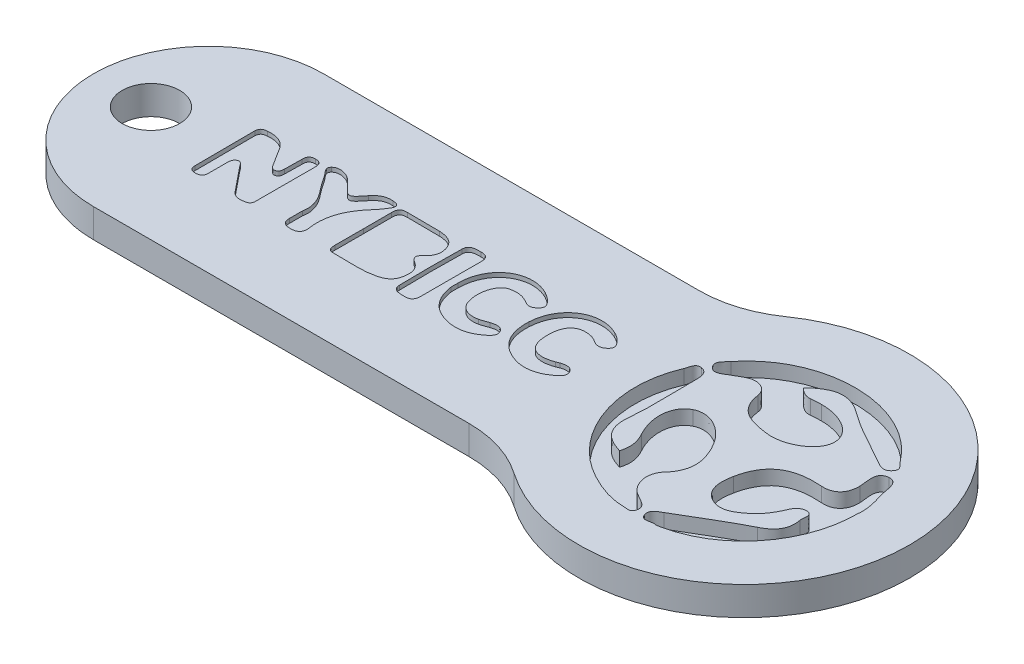
SolidWorks part; units mm, degrees
ref_plane "Plan de face" through (0, 0, 0) normal (0, 0, 1) x (1, 0, 0)
ref_plane "Plan de dessus" through (0, 0, 0) normal (0, 1, 0) x (1, 0, 0)
ref_plane "Plan de droite" through (0, 0, 0) normal (1, 0, 0) x (0, 0, -1)
sketch "Esquisse1" plane through (0, 0, 0) normal (0, 1, 0) x (1, 0, 0)
  line L0 (-14.5, 0) -> (0, 0) construction
  line L1 (-18.5, 8) -> (18.5, 8)
  line L2 (-18.5, 8) -> (-18.5, -8)
  line L3 (-18.5, -8) -> (18.5, -8)
  line L5 (-18.5, 8) -> (18.5, -8) construction
  line L6 (-18.5, -8) -> (18.5, 8) construction
  arc A0 (18.5, -8) -> (18.5, 8) centre (26.7614, 0) ccw
  circle A1 centre (-14.5, 0) radius 2
  point P0 (0, 0)
  dimension "D3" = 23
  dimension "D5" = 4
  dimension "D1" = 37
  dimension "D2" = 16
  dimension "D4" = 4
extrude "Boss.-Extru.1" add sketch "Esquisse1" along normal blind 2
sketch "Esquisse2" plane through (0, 2, 0) normal (0, 1, 0) x (1, 0, 0)
  line L0 (20.6551, -5.913) -> (-11.0872, -5.913)
  line L1 (-11.0872, -5.913) -> (-11.0872, 5.913)
  line L2 (-11.0872, 5.913) -> (20.6551, 5.913)
  line L3 (20.6551, 5.913) -> (20.5787, 5.7726)
  line L7 (18.5, 8) -> (-18.5, 8)
  line L8 (-18.5, 8) -> (-18.5, -8)
  line L9 (-18.5, -8) -> (18.5, -8)
  line L10 (18.5, 8) -> (-18.5, 8)
  line L11 (-18.5, 8) -> (-18.5, -8)
  line L12 (-18.5, -8) -> (18.5, -8)
  arc A2 (20.6551, -5.913) -> (20.6551, 5.913) centre (26.7614, 0) ccw
  arc A3 (20.6551, -5.913) -> (20.6551, 5.913) centre (26.7614, 0) ccw
  arc A4 (18.5, -8) -> (18.5, 8) centre (26.7614, 0) ccw
  arc A5 (18.5, -8) -> (18.5, 8) centre (26.7614, 0) ccw
  spline S0 degree 3 poles (0.225, -1.9246) (0.2286, -1.2609) (0.2275, -0.5975) (0.2283, 0.0661) knots 10 10 10 10 11 11 11 11
  spline S1 degree 3 poles (0.6284, -2.4527) (0.2813, -2.4644) (0.2234, -2.2089) (0.225, -1.9246) knots 9 9 9 9 10 10 10 10
  spline S2 degree 3 poles (3.5067, -2.3468) (2.5542, -2.5708) (1.5879, -2.4206) (0.6284, -2.4527) knots 8 8 8 8 9 9 9 9
  spline S3 degree 3 poles (4.4683, -1.5249) (4.3523, -2.028) (3.9703, -2.238) (3.5067, -2.3468) knots 7 7 7 7 8 8 8 8
  spline S4 degree 3 poles (4.0132, -0.175) (4.5319, -0.4973) (4.5922, -0.9877) (4.4683, -1.5249) knots 6 6 6 6 7 7 7 7
  spline S5 degree 3 poles (3.9341, 0.5259) (3.6149, 0.2483) (3.6818, 0.0309) (4.0132, -0.175) knots 5 5 5 5 6 6 6 6
  spline S6 degree 3 poles (4.2394, 1.8576) (4.4545, 1.3474) (4.3569, 0.8935) (3.9341, 0.5259) knots 4 4 4 4 5 5 5 5
  spline S7 degree 3 poles (3.0323, 2.5476) (3.5345, 2.5261) (4.0161, 2.3873) (4.2394, 1.8576) knots 3 3 3 3 4 4 4 4
  spline S8 degree 3 poles (0.7853, 2.5646) (1.5338, 2.5425) (2.2844, 2.5795) (3.0323, 2.5476) knots 2 2 2 2 3 3 3 3
  spline S9 degree 3 poles (0.2259, 1.9923) (0.215, 2.3984) (0.3606, 2.5772) (0.7853, 2.5646) knots 1 1 1 1 2 2 2 2
  spline S10 degree 3 poles (0.2283, 0.0661) (0.2291, 0.7082) (0.243, 1.3507) (0.2259, 1.9923) knots 0 0 0 0 1 1 1 1
  spline S11 degree 3 poles (-5.1722, 2.1197) (-5.1775, 1.4133) (-5.1754, 0.7068) (-5.176, 0.0003) knots 18 18 18 18 19 19 19 19
  spline S12 degree 3 poles (-5.6399, 2.5867) (-5.3196, 2.5835) (-5.1698, 2.4412) (-5.1722, 2.1197) knots 17 17 17 17 18 18 18 18
  spline S13 degree 3 poles (-6.0939, 2.115) (-6.0989, 2.4345) (-5.9709, 2.5902) (-5.6399, 2.5867) knots 16 16 16 16 17 17 17 17
  spline S14 degree 3 poles (-6.114, 0.896) (-6.0883, 1.3013) (-6.0877, 1.7087) (-6.0939, 2.115) knots 15 15 15 15 16 16 16 16
  spline S15 degree 3 poles (-6.3567, 0.4874) (-6.1454, 0.5282) (-6.1242, 0.7367) (-6.114, 0.896) knots 14 14 14 14 15 15 15 15
  spline S16 degree 3 poles (-6.7563, 0.7516) (-6.663, 0.6061) (-6.5561, 0.4488) (-6.3567, 0.4874) knots 13 13 13 13 14 14 14 14
  spline S17 degree 3 poles (-7.4724, 1.8877) (-7.2442, 1.5028) (-6.998, 1.1285) (-6.7563, 0.7516) knots 12 12 12 12 13 13 13 13
  spline S18 degree 3 poles (-8.9993, 2.5914) (-8.3468, 2.6534) (-7.8223, 2.4779) (-7.4724, 1.8877) knots 11 11 11 11 12 12 12 12
  spline S19 degree 3 poles (-9.4508, 2.1725) (-9.4369, 2.4583) (-9.2899, 2.5782) (-8.9993, 2.5914) knots 10 10 10 10 11 11 11 11
  spline S20 degree 3 poles (-9.4291, -2.0014) (-9.4372, -0.6101) (-9.4441, 0.7812) (-9.4508, 2.1725) knots 9 9 9 9 10 10 10 10
  spline S21 degree 3 poles (-9.0021, -2.437) (-9.2963, -2.4301) (-9.4357, -2.2901) (-9.4291, -2.0014) knots 8 8 8 8 9 9 9 9
  spline S22 degree 3 poles (-8.5069, -2.0014) (-8.512, -2.3343) (-8.6938, -2.4441) (-9.0021, -2.437) knots 7 7 7 7 8 8 8 8
  spline S23 degree 3 poles (-8.5036, -0.717) (-8.5043, -1.1452) (-8.5101, -1.5733) (-8.5069, -2.0014) knots 6 6 6 6 7 7 7 7
  spline S24 degree 3 poles (-8.2858, -0.219) (-8.4821, -0.3042) (-8.5032, -0.5178) (-8.5036, -0.717) knots 5 5 5 5 6 6 6 6
  spline S25 degree 3 poles (-7.8369, -0.4857) (-7.953, -0.3438) (-8.0529, -0.1181) (-8.2858, -0.219) knots 4 4 4 4 5 5 5 5
  spline S26 degree 3 poles (-6.4635, -2.1807) (-6.9172, -1.6123) (-7.376, -1.0481) (-7.8369, -0.4857) knots 3 3 3 3 4 4 4 4
  spline S27 degree 3 poles (-5.4688, -2.4272) (-5.8242, -2.5108) (-6.1923, -2.5206) (-6.4635, -2.1807) knots 2 2 2 2 3 3 3 3
  spline S28 degree 3 poles (-5.1794, -1.7337) (-5.182, -2.003) (-5.1008, -2.3406) (-5.4688, -2.4272) knots 1 1 1 1 2 2 2 2
  spline S29 degree 3 poles (-5.176, 0.0003) (-5.1766, -0.5777) (-5.174, -1.1557) (-5.1794, -1.7337) knots 0 0 0 0 1 1 1 1
  spline S30 degree 3 poles (14.6022, 1.5071) (13.5928, 1.7408) (13.0414, 1.2329) (13.0294, 0.0773) knots 11 11 11 11 12 12 12 12
  spline S31 degree 3 poles (15.1149, 1.2613) (14.9529, 1.3592) (14.7827, 1.4653) (14.6022, 1.5071) knots 10 10 10 10 11 11 11 11
  spline S32 degree 3 poles (15.9779, 1.4079) (15.76, 1.1539) (15.4505, 1.0583) (15.1149, 1.2613) knots 9 9 9 9 10 10 10 10
  spline S33 degree 3 poles (15.7902, 2.127) (15.9828, 1.9215) (16.214, 1.683) (15.9779, 1.4079) knots 8 8 8 8 9 9 9 9
  spline S34 degree 3 poles (15.1624, 2.5592) (15.3993, 2.452) (15.6134, 2.3158) (15.7902, 2.127) knots 7 7 7 7 8 8 8 8
  spline S35 degree 3 poles (11.588, 0.203) (11.6856, 2.2051) (13.4456, 3.3361) (15.1624, 2.5592) knots 6 6 6 6 7 7 7 7
  spline S36 degree 3 poles (12.9311, -2.3704) (11.8989, -1.8387) (11.5353, -0.8789) (11.588, 0.203) knots 5 5 5 5 6 6 6 6
  spline S37 degree 3 poles (15.6465, -2.1778) (14.7863, -2.8026) (13.8563, -2.8469) (12.9311, -2.3704) knots 4 4 4 4 5 5 5 5
  spline S38 degree 3 poles (16.0103, -1.3913) (16.2116, -1.7555) (15.9033, -1.9912) (15.6465, -2.1778) knots 3 3 3 3 4 4 4 4
  spline S39 degree 3 poles (15.1543, -1.1929) (15.4802, -1.0869) (15.8296, -1.0644) (16.0103, -1.3913) knots 2 2 2 2 3 3 3 3
  spline S40 degree 3 poles (14.9188, -1.2919) (14.9993, -1.2645) (15.0736, -1.2191) (15.1543, -1.1929) knots 1 1 1 1 2 2 2 2
  spline S41 degree 3 poles (13.0294, 0.0773) (13.0157, -1.2291) (13.6832, -1.7132) (14.9188, -1.2919) knots 0 0 0 0 1 1 1 1
  spline S42 degree 3 poles (6.7883, -0.4372) (6.7642, -0.2695) (6.7853, -0.0953) (6.7855, 0.0759) knots 13 13 13 13 14 14 14 14
  spline S43 degree 3 poles (8.2655, -2.4564) (7.3765, -2.0939) (6.9224, -1.3698) (6.7883, -0.4372) knots 12 12 12 12 13 13 13 13
  spline S44 degree 3 poles (10.8143, -2.1643) (10.0263, -2.763) (9.1527, -2.8182) (8.2655, -2.4564) knots 11 11 11 11 12 12 12 12
  spline S45 degree 3 poles (11.1531, -1.3675) (11.3657, -1.7257) (11.0713, -1.969) (10.8143, -2.1643) knots 10 10 10 10 11 11 11 11
  spline S46 degree 3 poles (10.2831, -1.1939) (10.6037, -1.0968) (10.9594, -1.0413) (11.1531, -1.3675) knots 9 9 9 9 10 10 10 10
  spline S47 degree 3 poles (9.6778, -1.3958) (9.8846, -1.3539) (10.0795, -1.2556) (10.2831, -1.1939) knots 8 8 8 8 9 9 9 9
  spline S48 degree 3 poles (8.2731, -0.709) (8.4644, -1.2666) (8.9952, -1.5338) (9.6778, -1.3958) knots 7 7 7 7 8 8 8 8
  spline S49 degree 3 poles (8.7857, 1.4455) (8.2295, 1.1729) (7.9857, 0.1288) (8.2731, -0.709) knots 6 6 6 6 7 7 7 7
  spline S50 degree 3 poles (9.155, 1.5328) (9.0302, 1.5112) (8.8966, 1.4998) (8.7857, 1.4455) knots 5 5 5 5 6 6 6 6
  spline S51 degree 3 poles (10.3714, 1.2365) (9.9944, 1.4594) (9.6027, 1.6104) (9.155, 1.5328) knots 4 4 4 4 5 5 5 5
  spline S52 degree 3 poles (11.1159, 1.4051) (10.9208, 1.1953) (10.6661, 1.0622) (10.3714, 1.2365) knots 3 3 3 3 4 4 4 4
  spline S53 degree 3 poles (10.9947, 2.0797) (11.1716, 1.8988) (11.3491, 1.6561) (11.1159, 1.4051) knots 2 2 2 2 3 3 3 3
  spline S54 degree 3 poles (10.3813, 2.5334) (10.6062, 2.4205) (10.8187, 2.2596) (10.9947, 2.0797) knots 1 1 1 1 2 2 2 2
  spline S55 degree 3 poles (6.7855, 0.0759) (6.7712, 2.1623) (8.6141, 3.4209) (10.3813, 2.5334) knots 0 0 0 0 1 1 1 1
  spline S56 degree 3 poles (20.8247, -2.0529) (20.69, -3.4272) (21.2917, -4.0532) (22.4958, -4.411) knots 13 13 13 13 14 14 14 14
  spline S57 degree 3 poles (20.8707, 2.5877) (20.8518, 1.04) (20.975, -0.5195) (20.8247, -2.0529) knots 12 12 12 12 13 13 13 13
  spline S58 degree 3 poles (20.3589, 3.4373) (20.7757, 3.356) (20.8759, 3.0031) (20.8707, 2.5877) knots 11 11 11 11 12 12 12 12
  spline S59 degree 3 poles (19.7877, 2.7925) (19.904, 3.0638) (19.9018, 3.5264) (20.3589, 3.4373) knots 10 10 10 10 11 11 11 11
  spline S60 degree 3 poles (23.1867, -6.7698) (19.8096, -4.9332) (18.3001, -0.6793) (19.7877, 2.7925) knots 9 9 9 9 10 10 10 10
  spline S61 degree 3 poles (25.9567, -7.6289) (24.9549, -7.6033) (24.0484, -7.2383) (23.1867, -6.7698) knots 8 8 8 8 9 9 9 9
  spline S62 degree 3 poles (26.6612, -7.3752) (26.5599, -7.7864) (26.214, -7.6353) (25.9567, -7.6289) knots 7 7 7 7 8 8 8 8
  spline S63 degree 3 poles (26.268, -6.6952) (26.5299, -6.8467) (26.7435, -7.0408) (26.6612, -7.3752) knots 6 6 6 6 7 7 7 7
  spline S64 degree 3 poles (25.7401, -6.3888) (25.9117, -6.4978) (26.0918, -6.5935) (26.268, -6.6952) knots 5 5 5 5 6 6 6 6
  spline S65 degree 3 poles (25.3508, -4.1307) (24.7364, -4.8112) (24.986, -5.9092) (25.7401, -6.3888) knots 4 4 4 4 5 5 5 5
  spline S66 degree 3 poles (25.5618, -1.0872) (26.0741, -2.135) (26.252, -3.1326) (25.3508, -4.1307) knots 3 3 3 3 4 4 4 4
  spline S67 degree 3 poles (22.5765, 0.6204) (23.5077, 1.0885) (24.8768, 0.3142) (25.5618, -1.0872) knots 2 2 2 2 3 3 3 3
  spline S68 degree 3 poles (22.2705, -2.6617) (21.4852, -1.2334) (21.6533, 0.1562) (22.5765, 0.6204) knots 1 1 1 1 2 2 2 2
  spline S69 degree 3 poles (22.4958, -4.411) (22.6895, -3.7654) (22.5874, -3.2375) (22.2705, -2.6617) knots 0 0 0 0 1 1 1 1
  spline S70 degree 3 poles (34.2908, 1.9196) (34.5116, 1.2692) (34.6572, 0.5833) (34.5723, 0.043) knots 15 15 15 15 16 16 16 16
  spline S71 degree 3 poles (33.4768, 3.345) (34.1825, 3.4033) (34.1107, 2.4507) (34.2908, 1.9196) knots 14 14 14 14 15 15 15 15
  spline S72 degree 3 poles (32.9899, 1.8117) (32.9782, 2.3605) (32.6504, 3.2769) (33.4768, 3.345) knots 13 13 13 13 14 14 14 14
  spline S73 degree 3 poles (31.6503, 0.4778) (32.418, 0.4191) (33.0107, 0.8361) (32.9899, 1.8117) knots 12 12 12 12 13 13 13 13
  spline S74 degree 3 poles (28.0087, -2.0014) (28.3864, -0.1074) (29.5871, 0.6354) (31.6503, 0.4778) knots 11 11 11 11 12 12 12 12
  spline S75 degree 3 poles (28.7232, -4.1459) (27.8705, -3.6814) (27.8418, -2.8385) (28.0087, -2.0014) knots 10 10 10 10 11 11 11 11
  spline S76 degree 3 poles (30.8285, -3.6402) (30.2151, -4.1482) (29.5238, -4.582) (28.7232, -4.1459) knots 9 9 9 9 10 10 10 10
  spline S77 degree 3 poles (31.9149, -2.0477) (31.6643, -2.6604) (31.3386, -3.2179) (30.8285, -3.6402) knots 8 8 8 8 9 9 9 9
  spline S78 degree 3 poles (32.6672, -1.5283) (32.3502, -1.494) (32.0434, -1.7332) (31.9149, -2.0477) knots 7 7 7 7 8 8 8 8
  spline S79 degree 3 poles (32.9603, -2.3153) (32.9084, -2.0339) (33.1548, -1.5813) (32.6672, -1.5283) knots 6 6 6 6 7 7 7 7
  spline S80 degree 3 poles (31.9014, -4.2266) (32.7588, -3.7947) (33.1312, -3.2385) (32.9603, -2.3153) knots 5 5 5 5 6 6 6 6
  spline S81 degree 3 poles (27.7784, -6.5813) (29.1518, -5.7938) (30.49, -4.9378) (31.9014, -4.2266) knots 4 4 4 4 5 5 5 5
  spline S82 degree 3 poles (27.221, -7.3854) (27.066, -6.9234) (27.4568, -6.7657) (27.7784, -6.5813) knots 3 3 3 3 4 4 4 4
  spline S83 degree 3 poles (28.1667, -7.6063) (27.8477, -7.5375) (27.3951, -7.903) (27.221, -7.3854) knots 2 2 2 2 3 3 3 3
  spline S84 degree 3 poles (28.5281, -7.569) (28.4093, -7.5932) (28.2794, -7.6307) (28.1667, -7.6063) knots 1 1 1 1 2 2 2 2
  spline S85 degree 3 poles (34.5723, 0.043) (34.5572, -3.6847) (31.9805, -6.8615) (28.5281, -7.569) knots 0 0 0 0 1 1 1 1
  spline S86 degree 3 poles (-2.9715, -1.8867) (-2.973, -1.6296) (-2.9712, -1.3724) (-2.9707, -0.9865) knots 12 12 12 12 13 13 13 13
  spline S87 degree 3 poles (-2.3827, -2.4792) (-2.7888, -2.4647) (-2.9692, -2.2761) (-2.9715, -1.8867) knots 11 11 11 11 12 12 12 12
  spline S88 degree 3 poles (-1.7083, -1.7964) (-1.6343, -2.2893) (-1.886, -2.4971) (-2.3827, -2.4792) knots 10 10 10 10 11 11 11 11
  spline S89 degree 3 poles (-0.5499, 1.5886) (-1.4324, 0.6279) (-1.9089, -0.4619) (-1.7083, -1.7964) knots 9 9 9 9 10 10 10 10
  spline S90 degree 3 poles (-0.1364, 2.159) (-0.265, 1.9625) (-0.392, 1.7605) (-0.5499, 1.5886) knots 8 8 8 8 9 9 9 9
  spline S91 degree 3 poles (-0.4448, 2.7623) (0.0585, 2.7305) (0.1083, 2.5327) (-0.1364, 2.159) knots 7 7 7 7 8 8 8 8
  spline S92 degree 3 poles (-1.5894, 2.2197) (-1.281, 2.6095) (-0.9475, 2.7942) (-0.4448, 2.7623) knots 6 6 6 6 7 7 7 7
  spline S93 degree 3 poles (-2.9946, 2.1544) (-2.2746, 1.3894) (-2.2599, 1.3721) (-1.5894, 2.2197) knots 5 5 5 5 6 6 6 6
  spline S94 degree 3 poles (-3.569, 2.6592) (-3.3482, 2.549) (-3.1695, 2.3403) (-2.9946, 2.1544) knots 4 4 4 4 5 5 5 5
  spline S95 degree 3 poles (-4.5969, 2.6437) (-4.3452, 2.899) (-3.899, 2.8238) (-3.569, 2.6592) knots 3 3 3 3 4 4 4 4
  spline S96 degree 3 poles (-4.318, 1.8864) (-4.4694, 2.1215) (-4.86, 2.3768) (-4.5969, 2.6437) knots 2 2 2 2 3 3 3 3
  spline S97 degree 3 poles (-3.6134, 0.892) (-3.8691, 1.2068) (-4.0981, 1.5451) (-4.318, 1.8864) knots 1 1 1 1 2 2 2 2
  spline S98 degree 3 poles (-2.9707, -0.9865) (-2.8232, -0.3301) (-3.1349, 0.3025) (-3.6134, 0.892) knots 0 0 0 0 1 1 1 1
  spline S99 degree 3 poles (28.4489, 6.1036) (27.188, 7.04) (26.1934, 6.8331) (25.1006, 5.7726) knots 13 13 13 13 14 14 14 14
  spline S100 degree 3 poles (32.2257, 3.8741) (30.9697, 4.6247) (29.6158, 5.2371) (28.4489, 6.1036) knots 12 12 12 12 13 13 13 13
  spline S101 degree 3 poles (33.1947, 3.8749) (32.8996, 3.5244) (32.5762, 3.6646) (32.2257, 3.8741) knots 11 11 11 11 12 12 12 12
  spline S102 degree 3 poles (32.9181, 4.6879) (33.0852, 4.4632) (33.51, 4.2491) (33.1947, 3.8749) knots 10 10 10 10 11 11 11 11
  spline S103 degree 3 poles (21.0052, 4.8289) (23.9283, 8.5635) (30.0923, 8.4884) (32.9181, 4.6879) knots 9 9 9 9 10 10 10 10
  spline S104 degree 3 poles (20.6512, 3.9116) (20.3706, 4.3111) (20.8091, 4.5784) (21.0052, 4.8289) knots 8 8 8 8 9 9 9 9
  spline S105 degree 3 poles (21.7112, 3.951) (21.3602, 3.7373) (20.9758, 3.4496) (20.6512, 3.9116) knots 7 7 7 7 8 8 8 8
  spline S106 degree 3 poles (22.4531, 4.3729) (22.1989, 4.2458) (21.9541, 4.099) (21.7112, 3.951) knots 6 6 6 6 7 7 7 7
  spline S107 degree 3 poles (23.9755, 3.7431) (23.8907, 4.348) (23.204, 4.7486) (22.4531, 4.3729) knots 5 5 5 5 6 6 6 6
  spline S108 degree 3 poles (26.5035, 1.7576) (25.3358, 1.9291) (24.1957, 2.1695) (23.9755, 3.7431) knots 4 4 4 4 5 5 5 5
  spline S109 degree 3 poles (29.457, 3.5205) (29.4094, 2.5046) (27.9199, 1.5498) (26.5035, 1.7576) knots 3 3 3 3 4 4 4 4
  spline S110 degree 3 poles (26.7445, 5.4024) (28.3033, 5.391) (29.5054, 4.5538) (29.457, 3.5205) knots 2 2 2 2 3 3 3 3
  spline S111 degree 3 poles (26.0136, 5.3603) (26.2569, 5.3802) (26.5009, 5.4042) (26.7445, 5.4024) knots 1 1 1 1 2 2 2 2
  spline S112 degree 3 poles (25.1006, 5.7726) (25.3972, 5.4799) (25.6664, 5.3319) (26.0136, 5.3603) knots 0 0 0 0 1 1 1 1
  spline S113 degree 3 poles (6.2957, 2.1656) (6.2889, 1.4614) (6.2923, 0.7571) (6.2917, 0.0529) knots 6 6 6 6 7 7 7 7
  spline S114 degree 3 poles (5.7113, 2.7436) (6.1126, 2.754) (6.2995, 2.5672) (6.2957, 2.1656) knots 5 5 5 5 6 6 6 6
  spline S115 degree 3 poles (4.8778, 2.2684) (4.8908, 2.7581) (5.3424, 2.734) (5.7113, 2.7436) knots 4 4 4 4 5 5 5 5
  spline S116 degree 3 poles (4.8746, -2.0826) (4.8408, -0.6328) (4.8396, 0.8188) (4.8778, 2.2684) knots 3 3 3 3 4 4 4 4
  spline S117 degree 3 poles (5.7365, -2.5991) (5.3325, -2.5938) (4.8868, -2.606) (4.8746, -2.0826) knots 2 2 2 2 3 3 3 3
  spline S118 degree 3 poles (6.2899, -1.9959) (6.2905, -2.369) (6.1719, -2.6048) (5.7365, -2.5991) knots 1 1 1 1 2 2 2 2
  spline S119 degree 3 poles (6.2917, 0.0529) (6.2911, -0.63) (6.2888, -1.313) (6.2899, -1.9959) knots 0 0 0 0 1 1 1 1
  dimension "D1" = 3
  dimension "D2" = 0
sketch "Esquisse3" plane through (0, 2, 0) normal (0, 1, 0) x (1, 0, 0)
  line L0 (-18.5, -8) -> (18.5, -8) construction
  line L1 (18.5, 8) -> (-18.5, 8) construction
  line L2 (-18.5, 8) -> (-18.5, -8) construction
  line L3 (-18.5, -8) -> (18.5, -8)
  line L4 (18.5, 8) -> (-18.5, 8)
  line L5 (-18.5, 8) -> (-18.5, -8)
  line L6 (20.6551, -5.913) -> (-11.0872, -5.913) construction
  line L7 (-11.0872, -5.913) -> (-11.0872, 5.913) construction
  line L8 (-11.0872, 5.913) -> (20.6551, 5.913) construction
  line L9 (20.6551, -5.913) -> (-11.0872, -5.913)
  line L10 (-11.0872, -5.913) -> (-11.0872, 5.913)
  line L11 (-11.0872, 5.913) -> (20.6551, 5.913)
  arc A0 (18.5, -8) -> (18.5, 8) centre (26.7614, 0) ccw construction
  arc A1 (18.5, -8) -> (18.5, 8) centre (26.7614, 0) ccw
  arc A2 (20.6551, -5.913) -> (20.6551, 5.913) centre (26.7614, 0) ccw construction
  arc A3 (20.6551, -5.913) -> (20.6551, 5.913) centre (26.7614, 0) ccw
  circle A4 centre (-14.5, 0) radius 2 construction
  circle A5 centre (-14.5, 0) radius 2
sketch "Esquisse4" plane through (0, 2, 0) normal (0, 1, 0) x (1, 0, 0)
  line L0 (20.6551, 5.913) -> (20.5787, 5.7726) construction
  line L7 (20.6551, 5.913) -> (20.5787, 5.7726)
  spline S0 degree 3 poles (-1984.6159, -235.4176) (1984.8667, 57.9946) (-1984.2687, -59.6643) (1984.6454, 236.3676) knots -55.998309 -55.998309 -55.998309 -55.998309 77.422102 77.422102 77.422102 77.422102 only from (0.225, -1.9246) to (0.2283, 0.0661) construction
  spline S1 degree 3 poles (1999.7349, -15.7658) (-1999.9355, -74.5215) (2000.3921, 75.7285) (-1999.2541, 17.2511) knots -35.375256 -35.375256 -35.375256 -35.375256 35.969237 35.969237 35.969237 35.969237 only from (0.2283, 0.0661) to (0.2259, 1.9923) construction
  spline S2 degree 3 poles (-1692.3905, -1052.1639) (1808.7885, 680.6818) (-1908.2396, -373.9881) (1993.8725, 140.0338) knots -24.33099 -24.33099 -24.33099 -24.33099 25.117482 25.117482 25.117482 25.117482 only from (0.2259, 1.9923) to (0.7853, 2.5646) construction
  spline S3 degree 3 poles (21.6545, 2002.1445) (-93.1428, -1997.5504) (96.9755, 2002.6751) (-18.569, -1997.045) knots -22.540346 -22.540346 -22.540346 -22.540346 27.463763 27.463763 27.463763 27.463763 only from (0.7853, 2.5646) to (3.0323, 2.5476) construction
  spline S4 degree 3 poles (1342.8316, 1487.3667) (-1343.1752, -1508.655) (1318.8645, 1538.4795) (-1249.0693, -1556.4903) knots -15.00696 -15.00696 -15.00696 -15.00696 20.437547 20.437547 20.437547 20.437547 only from (3.0323, 2.5476) to (4.2394, 1.8576) construction
  spline S5 degree 3 poles (-758.8387, -1790.0698) (-384.1825, 1710.4209) (1110.0246, -1522.0891) (-1512.5494, 1293.8524) knots -37.495623 -37.495623 -37.495623 -37.495623 37.718737 37.718737 37.718737 37.718737 only from (4.2394, 1.8576) to (3.9341, 0.5259) construction
  spline S6 degree 3 poles (1901.3277, 632.4127) (-1933.3024, -702.9617) (1907.3667, 801.0653) (-1760.1231, -939.1778) knots -17.085348 -17.085348 -17.085348 -17.085348 32.880542 32.880542 32.880542 32.880542 only from (3.9341, 0.5259) to (4.0132, -0.175) construction
  spline S7 degree 3 poles (-1846.1792, -759.1673) (1864.6087, 816.5198) (-1848.0317, -842.6889) (1829.127, 817.172) knots -11.270564 -11.270564 -11.270564 -11.270564 26.527108 26.527108 26.527108 26.527108 only from (4.0132, -0.175) to (4.4683, -1.5249) construction
  spline S8 degree 3 poles (-1354.7293, 1465.4733) (1405.9497, -1460.4078) (-1406.7612, 1449.9158) (1379.4873, -1453.6486) knots -11.155139 -11.155139 -11.155139 -11.155139 28.131848 28.131848 28.131848 28.131848 only from (4.4683, -1.5249) to (3.5067, -2.3468) construction
  spline S9 degree 3 poles (-28.5631, 1997.2346) (90.6759, -2003.8054) (-87.5575, 1998.8408) (31.7925, -2002.0232) knots -6.648346 -6.648346 -6.648346 -6.648346 23.992993 23.992993 23.992993 23.992993 only from (3.5067, -2.3468) to (0.6284, -2.4527) construction
  spline S10 degree 3 poles (1411.4689, 1415.0021) (-1401.3499, -1450.1488) (1390.9958, 1457.3173) (-1378.561, -1450.6074) knots -8.05933 -8.05933 -8.05933 -8.05933 28.435848 28.435848 28.435848 28.435848 only from (0.6284, -2.4527) to (0.225, -1.9246) construction
  spline S11 degree 3 poles (-97.8956, -1981.1768) (690.426, 1506.3572) (-1281.6463, -874.2833) (1979.2178, 67.1058) knots -10.529402 -10.529402 -10.529402 -10.529402 35.566895 35.566895 35.566895 35.566895 only from (14.6022, 1.5071) to (13.0294, 0.0773) construction
  spline S12 degree 3 poles (1949.7679, 398.3881) (-1397.5696, 433.0176) (848.2959, -1224.1896) (-194.4399, 1965.5178) knots -20.941126 -20.941126 -20.941126 -20.941126 21.868417 21.868417 21.868417 21.868417 only from (13.0294, 0.0773) to (14.9188, -1.2919) construction
  spline S13 degree 3 poles (-635.9133, 1889.7913) (654.3027, -1897.7039) (-624.0515, 1895.283) (665.4221, -1892.4779) knots -35.600819 -35.600819 -35.600819 -35.600819 38.569409 38.569409 38.569409 38.569409 only from (14.9188, -1.2919) to (15.1543, -1.1929) construction
  spline S14 degree 3 poles (1232.8348, 1585.2896) (-1188.5596, -1623.3311) (1181.3523, 1647.1031) (-1091.2599, -1666.6185) knots -16.478794 -16.478794 -16.478794 -16.478794 20.145313 20.145313 20.145313 20.145313 only from (15.1543, -1.1929) to (16.0103, -1.3913) construction
  spline S15 degree 3 poles (-1956.7943, 326.691) (2007.9741, -293.3837) (-1980.3817, 263.4136) (1999.6702, -253.8499) knots -11.326247 -11.326247 -11.326247 -11.326247 19.171764 19.171764 19.171764 19.171764 only from (16.0103, -1.3913) to (15.6465, -2.1778) construction
  spline S16 degree 3 poles (-972.4429, 1730.2132) (1342.4303, -1518.7994) (-1656.7274, 1035.2434) (1969.7851, -170.5391) knots -19.231438 -19.231438 -19.231438 -19.231438 35.06852 35.06852 35.06852 35.06852 only from (15.6465, -2.1778) to (12.9311, -2.3704) construction
  spline S17 degree 3 poles (1450.3278, 1386.8956) (-1356.7136, -1547.8282) (1271.6623, 1649.3112) (-1094.442, -1665.2911) knots -10.368146 -10.368146 -10.368146 -10.368146 24.205438 24.205438 24.205438 24.205438 only from (12.9311, -2.3704) to (11.588, 0.203) construction
  spline S18 degree 3 poles (1916.8799, 594.4821) (-1777.8783, -899.8956) (1637.4032, 1178.5364) (-1393.7476, -1411.3134) knots -3.492496 -3.492496 -3.492496 -3.492496 16.464951 16.464951 16.464951 16.464951 only from (11.588, 0.203) to (15.1624, 2.5592) construction
  spline S19 degree 3 poles (1002.5446, 1741.5536) (-1033.0456, -1715.8116) (1074.7683, 1713.6368) (-1014.5815, -1711.94) knots -35.983375 -35.983375 -35.983375 -35.983375 47.351842 47.351842 47.351842 47.351842 only from (15.1624, 2.5592) to (15.7902, 2.127) construction
  spline S20 degree 3 poles (2015.7301, 1.4994) (-1996.1954, -0.7141) (2027.6138, 21.579) (-1983.3114, -47.4545) knots -7.760073 -7.760073 -7.760073 -7.760073 23.910839 23.910839 23.910839 23.910839 only from (15.7902, 2.127) to (15.9779, 1.4079) construction
  spline S21 degree 3 poles (-1056.2118, -1685.326) (944.4563, 1797.9971) (-761.5857, -1864.2446) (637.7935, 1900.8501) knots -15.195035 -15.195035 -15.195035 -15.195035 31.84164 31.84164 31.84164 31.84164 only from (15.9779, 1.4079) to (15.1149, 1.2613) construction
  spline S22 degree 3 poles (69.3485, 2000.4781) (-34.7887, -2009.1821) (80.2974, 2011.1017) (-85.3785, -1995.8911) knots -20.144545 -20.144545 -20.144545 -20.144545 40.360841 40.360841 40.360841 40.360841 only from (15.1149, 1.2613) to (14.6022, 1.5071) construction
  spline S23 degree 3 poles (1991.5419, 97.7516) (-2002.0056, 32.259) (1991.6922, -33.2335) (-2002.0098, -98.7261) knots -56.370957 -56.370957 -56.370957 -56.370957 56.933317 56.933317 56.933317 56.933317 only from (-5.176, 0.0003) to (-5.1794, -1.7337) construction
  spline S24 degree 3 poles (1990.0705, 119.8329) (-2000.3981, 45.9324) (1989.9987, -44.8805) (-2000.2796, -118.3534) knots -39.486099 -39.486099 -39.486099 -39.486099 76.939646 76.939646 76.939646 76.939646 only from (-5.1722, 2.1197) to (-5.176, 0.0003) construction
  spline S25 degree 3 poles (-1514.7247, 1294.7036) (952.749, -1555.6921) (-514.9768, 1792.3506) (143.8851, -1987.0807) knots -18.57208 -18.57208 -18.57208 -18.57208 50.514202 50.514202 50.514202 50.514202 only from (-5.6399, 2.5867) to (-5.1722, 2.1197) construction
  spline S26 degree 3 poles (-1877.1306, -682.9309) (1933.1452, 262.2025) (-1979.9546, 51.1676) (1974.968, -263.0849) knots -15.916168 -15.916168 -15.916168 -15.916168 44.683452 44.683452 44.683452 44.683452 only from (-6.0939, 2.115) to (-5.6399, 2.5867) construction
  spline S27 degree 3 poles (-1984.625, 290.7016) (1972.6598, -373.7166) (-1983.3894, 389.401) (1967.9915, -317.242) knots -31.513147 -31.513147 -31.513147 -31.513147 64.250905 64.250905 64.250905 64.250905 only from (-6.114, 0.896) to (-6.0939, 2.115) construction
  spline S28 degree 3 poles (-1317.6023, 1510.4746) (1281.5296, -1540.6069) (-1271.0603, 1561.2131) (1237.2504, -1565.5542) knots -4.359551 -4.359551 -4.359551 -4.359551 34.141117 34.141117 34.141117 34.141117 only from (-6.3567, 0.4874) to (-6.114, 0.896) construction
  spline S29 degree 3 poles (-704.888, -1873.3767) (697.205, 1881.7156) (-724.356, -1874.9299) (732.3513, 1858.9379) knots -7.800082 -7.800082 -7.800082 -7.800082 33.854075 33.854075 33.854075 33.854075 only from (-6.7563, 0.7516) to (-6.3567, 0.4874) construction
  spline S30 degree 3 poles (1686.2531, 1064.9229) (-1741.5284, -998.6405) (1727.8868, 1000.3536) (-1700.5204, -1062.2751) knots -29.77822 -29.77822 -29.77822 -29.77822 55.385582 55.385582 55.385582 55.385582 only from (-7.4724, 1.8877) to (-6.7563, 0.7516) construction
  spline S31 degree 3 poles (349.9698, 1969.1657) (-518.8212, -1984.8781) (555.4811, 1972.3308) (-559.4658, -1920.3992) knots -12.744458 -12.744458 -12.744458 -12.744458 31.890927 31.890927 31.890927 31.890927 only from (-8.9993, 2.5914) to (-7.4724, 1.8877) construction
  spline S32 degree 3 poles (62.1842, -1994.5239) (156.3714, 1949.5866) (-487.3684, -1875.4729) (872.5158, 1790.3812) knots -19.56925 -19.56925 -19.56925 -19.56925 43.997523 43.997523 43.997523 43.997523 only from (-9.4508, 2.1725) to (-8.9993, 2.5914) construction
  spline S33 degree 3 poles (1868.568, -629.3467) (-1882.7149, -26.8581) (1862.2669, 29.7478) (-1882.8415, 640.3356) knots -109.086057 -109.086057 -109.086057 -109.086057 129.222482 129.222482 129.222482 129.222482 only from (-9.4291, -2.0014) to (-9.4508, 2.1725) construction
  spline S34 degree 3 poles (1858.5574, -646.0582) (-1085.6529, 1146.0776) (412.2247, -1596.9713) (105.5736, 1984.269) knots -37.811873 -37.811873 -37.811873 -37.811873 51.183123 51.183123 51.183123 51.183123 only from (-9.0021, -2.437) to (-9.4291, -2.0014) construction
  spline S35 degree 3 poles (-948.3287, 1763.2789) (906.1852, -1816.4719) (-849.586, 1848.2067) (691.9189, -1874.7093) knots -16.474382 -16.474382 -16.474382 -16.474382 35.183216 35.183216 35.183216 35.183216 only from (-8.5069, -2.0014) to (-9.0021, -2.437) construction
  spline S36 degree 3 poles (-2006.5388, 78.5807) (1990.0829, 8.6823) (-2007.117, -11.342) (1989.5957, -80.0299) knots -45.796593 -45.796593 -45.796593 -45.796593 58.515214 58.515214 58.515214 58.515214 only from (-8.5036, -0.717) to (-8.5069, -2.0014) construction
  spline S37 degree 3 poles (1488.0078, -1327.1249) (-1490.1443, 1358.907) (1458.2111, -1376.7866) (-1460.2368, 1374.8972) knots -15.192002 -15.192002 -15.192002 -15.192002 27.246672 27.246672 27.246672 27.246672 only from (-8.2858, -0.219) to (-8.5036, -0.717) construction
  spline S38 degree 3 poles (673.088, 1880.0131) (-688.1382, -1888.8072) (679.2484, 1885.4471) (-709.6456, -1873.1101) knots -12.426132 -12.426132 -12.426132 -12.426132 20.812048 20.812048 20.812048 20.812048 only from (-7.8369, -0.4857) to (-8.2858, -0.219) construction
  spline S39 degree 3 poles (-1484.655, -1345.5597) (1616.695, 1165.2864) (-1635.7671, -1162.0527) (1471.2106, 1341.657) knots -75.46992 -75.46992 -75.46992 -75.46992 84.90711 84.90711 84.90711 84.90711 only from (-6.4635, -2.1807) to (-7.8369, -0.4857) construction
  spline S40 degree 3 poles (-767.3684, -1851.5657) (756.8255, 1864.5842) (-741.1465, -1879.287) (678.4119, 1876.754) knots -17.146101 -17.146101 -17.146101 -17.146101 20.711154 20.711154 20.711154 20.711154 only from (-5.4688, -2.4272) to (-6.4635, -2.1807) construction
  spline S41 degree 3 poles (1710.8865, -1028.8932) (-1725.3117, 1036.0537) (1718.4132, -1033.9693) (-1731.5988, 1007.6235) knots -13.610126 -13.610126 -13.610126 -13.610126 15.95404 15.95404 15.95404 15.95404 only from (-5.1794, -1.7337) to (-5.4688, -2.4272) construction
  spline S42 degree 3 poles (-1967.5315, 288.8439) (2008.4862, -256.0698) (-1990.003, 227.1596) (1998.9442, -219.1607) knots -4.474592 -4.474592 -4.474592 -4.474592 26.362409 26.362409 26.362409 26.362409 only from (11.1531, -1.3675) to (10.8143, -2.1643) construction
  spline S43 degree 3 poles (1042.5899, 1711.7208) (-1017.4605, -1736.0585) (1011.4406, 1748.6428) (-942.6349, -1759.1398) knots -8.283647 -8.283647 -8.283647 -8.283647 26.187035 26.187035 26.187035 26.187035 only from (10.2831, -1.1939) to (11.1531, -1.3675) construction
  spline S44 degree 3 poles (-437.8676, 1947.8489) (436.7439, -1958.6073) (-417.5143, 1955.8514) (460.5386, -1949.8076) knots -18.995703 -18.995703 -18.995703 -18.995703 36.206708 36.206708 36.206708 36.206708 only from (9.6778, -1.3958) to (10.2831, -1.1939) construction
  spline S45 degree 3 poles (1927.2811, -546.9605) (-1762.1024, 866.6105) (1588.2179, -1178.8653) (-1333.8705, 1472.6681) knots -13.083599 -13.083599 -13.083599 -13.083599 28.316064 28.316064 28.316064 28.316064 only from (8.2731, -0.709) to (9.6778, -1.3958) construction
  spline S46 degree 3 poles (-210.3772, -1985.6489) (375.3341, 1996.5797) (-506.2668, -1963.0737) (668.3993, 1886.0938) knots -5.944932 -5.944932 -5.944932 -5.944932 19.309732 19.309732 19.309732 19.309732 only from (8.7857, 1.4455) to (8.2731, -0.709) construction
  spline S47 degree 3 poles (-1006.2355, 1724.5825) (1036.4975, -1721.3846) (-1014.2482, 1726.7744) (1012.0788, -1728.5937) knots -26.66818 -26.66818 -26.66818 -26.66818 37.096617 37.096617 37.096617 37.096617 only from (9.155, 1.5328) to (8.7857, 1.4455) construction
  spline S48 degree 3 poles (558.36, 1924.5437) (-497.6224, -1947.5948) (514.8773, 1950.5552) (-523.0983, -1926.1926) knots -19.60293 -19.60293 -19.60293 -19.60293 26.69759 26.69759 26.69759 26.69759 only from (10.3714, 1.2365) to (9.155, 1.5328) construction
  spline S49 degree 3 poles (-234.0396, -1983.3805) (213.7878, 2010.2476) (-135.5771, -2011.2908) (89.6481, 1999.4407) knots -17.879025 -17.879025 -17.879025 -17.879025 23.256703 23.256703 23.256703 23.256703 only from (11.1159, 1.4051) to (10.3714, 1.2365) construction
  spline S50 degree 3 poles (1988.0089, -299.9971) (-1982.2636, 281.7575) (2008.5743, -242.8377) (-1978.8999, 199.7886) knots -14.898875 -14.898875 -14.898875 -14.898875 18.938346 18.938346 18.938346 18.938346 only from (10.9947, 2.0797) to (11.1159, 1.4051) construction
  spline S51 degree 3 poles (1149.1378, -1640.841) (-1244.1275, 1598.2178) (1353.7759, -1521.2377) (-1391.1325, 1427.4966) knots -35.868788 -35.868788 -35.868788 -35.868788 39.412528 39.412528 39.412528 39.412528 only from (10.3813, 2.5334) to (10.9947, 2.0797) construction
  spline S52 degree 3 poles (1873.6773, 706.4025) (-1732.4564, -998.3848) (1573.6902, 1259.7264) (-1335.385, -1472.065) knots -9.011052 -9.011052 -9.011052 -9.011052 9.927219 9.927219 9.927219 9.927219 only from (6.7855, 0.0759) to (10.3813, 2.5334) construction
  spline S53 degree 3 poles (1989.1237, 264.591) (-1976.4031, -286.1239) (1989.9593, 285.9303) (-1975.5432, -264.7057) knots -17.366021 -17.366021 -17.366021 -17.366021 44.734209 44.734209 44.734209 44.734209 only from (6.7883, -0.4372) to (6.7855, 0.0759) construction
  spline S54 degree 3 poles (1360.9645, 1469.6546) (-1303.0246, -1642.4099) (1220.7915, 1735.773) (-1044.6378, -1701.0433) knots -7.240159 -7.240159 -7.240159 -7.240159 37.041661 37.041661 37.041661 37.041661 only from (8.2655, -2.4564) to (6.7883, -0.4372) construction
  spline S55 degree 3 poles (-695.3911, 1867.364) (948.9848, -1905.3632) (-1145.669, 1806.7791) (1304.7031, -1520.7203) knots -9.75022 -9.75022 -9.75022 -9.75022 38.85468 38.85468 38.85468 38.85468 only from (10.8143, -2.1643) to (8.2655, -2.4564) construction
  spline S86 degree 3 poles (-1996.5076, 141.1588) (1958.4781, 68.2051) (-1945.8353, -269.4825) (1940.1218, 475.3422) knots -5.817263 -5.817263 -5.817263 -5.817263 16.754081 16.754081 16.754081 16.754081 only from (-2.9946, 2.1544) to (-1.5894, 2.2197) construction
  spline S87 degree 3 poles (-641.9706, -1892.6293) (605.576, 1920.3367) (-599.2656, -1919.9937) (598.4023, 1909.5649) knots -20.238441 -20.238441 -20.238441 -20.238441 29.916052 29.916052 29.916052 29.916052 only from (-3.569, 2.6592) to (-2.9946, 2.1544) construction
  spline S88 degree 3 poles (1491.647, -1323.9265) (-1575.0482, 1273.0455) (1619.7481, -1201.2803) (-1655.0498, 1130.2487) knots -13.329862 -13.329862 -13.329862 -13.329862 21.145653 21.145653 21.145653 21.145653 only from (-4.5969, 2.6437) to (-3.569, 2.6592) construction
  spline S89 degree 3 poles (-2004.1624, 21.5012) (2006.5492, -24.0344) (-2015.54, 22.0299) (1995.3419, 1.1491) knots -10.833823 -10.833823 -10.833823 -10.833823 15.369819 15.369819 15.369819 15.369819 only from (-4.318, 1.8864) to (-4.5969, 2.6437) construction
  spline S90 degree 3 poles (1350.3935, 1472.4112) (-1310.1477, -1537.317) (1288.1578, 1553.6289) (-1320.5824, -1503.7216) knots -39.752568 -39.752568 -39.752568 -39.752568 44.370766 44.370766 44.370766 44.370766 only from (-3.6134, 0.892) to (-4.318, 1.8864) construction
  spline S91 degree 3 poles (-2002.1072, 46.3552) (2035.7466, -122.7975) (-2043.7224, 165.8489) (1989.7629, -160.7222) knots -17.511544 -17.511544 -17.511544 -17.511544 20.644046 20.644046 20.644046 20.644046 only from (-2.9707, -0.9865) to (-3.6134, 0.892) construction
  spline S92 degree 3 poles (75.0362, -2000.3374) (-76.7409, 1971.425) (66.7065, -1975.6299) (-68.7055, 1997.8755) knots -12.864931 -12.864931 -12.864931 -12.864931 36.870404 36.870404 36.870404 36.870404 only from (-2.9715, -1.8867) to (-2.9707, -0.9865) construction
  spline S93 degree 3 poles (1974.5413, -263.0072) (-1726.2809, 626.5559) (1434.1118, -1087.0319) (-1119.1512, 1640.459) knots -19.296752 -19.296752 -19.296752 -19.296752 44.947867 44.947867 44.947867 44.947867 only from (-2.3827, -2.4792) to (-2.9715, -1.8867) construction
  spline S94 degree 3 poles (-1562.8561, 1248.0481) (1713.75, -1296.104) (-1778.9314, 1260.7692) (1657.7895, -1117.4866) knots -13.308287 -13.308287 -13.308287 -13.308287 42.007396 42.007396 42.007396 42.007396 only from (-1.7083, -1.7964) to (-2.3827, -2.4792) construction
  spline S95 degree 3 poles (-1785.5122, 901.3781) (1920.25, -799.8958) (-1921.2058, 782.9226) (1828.2661, -808.1721) knots -11.551156 -11.551156 -11.551156 -11.551156 26.667592 26.667592 26.667592 26.667592 only from (-0.5499, 1.5886) to (-1.7083, -1.7964) construction
  spline S96 degree 3 poles (1348.6782, -1474.4179) (-1335.8849, 1501.5734) (1340.204, -1493.0178) (-1363.0557, 1465.5187) knots -26.53428 -26.53428 -26.53428 -26.53428 42.74763 42.74763 42.74763 42.74763 only from (-0.1364, 2.159) to (-0.5499, 1.5886) construction
  spline S97 degree 3 poles (-1996.1738, -119.5399) (2042.4716, 1.1534) (-2028.2429, 206.0193) (1927.6508, -513.3026) knots -13.587384 -13.587384 -13.587384 -13.587384 33.050213 33.050213 33.050213 33.050213 only from (-0.4448, 2.7623) to (-0.1364, 2.159) construction
  spline S98 degree 3 poles (-1985.5308, -225.688) (1940.3628, -46.8688) (-1931.5006, 280.081) (1944.3873, -458.8551) knots -18.061348 -18.061348 -18.061348 -18.061348 29.558102 29.558102 29.558102 29.558102 only from (-1.5894, 2.2197) to (-0.4448, 2.7623) construction
  spline S99 degree 3 poles (2003.3638, 89.3657) (-1990.8659, 58.6488) (2003.4284, -57.4641) (-1990.7189, -87.7038) knots -45.321078 -45.321078 -45.321078 -45.321078 58.753926 58.753926 58.753926 58.753926 only from (6.2957, 2.1656) to (6.2917, 0.0529) construction
  spline S100 degree 3 poles (-1990.1626, 80.7378) (2003.0482, 117.7931) (-1990.438, -118.7904) (2002.6577, -82.9177) knots -72.915593 -72.915593 -72.915593 -72.915593 73.598298 73.598298 73.598298 73.598298 only from (6.2917, 0.0529) to (6.2899, -1.9959) construction
  spline S101 degree 3 poles (1824.7477, -833.4905) (-1791.9792, 925.692) (1778.2156, -978.3178) (-1734.1031, 983.6974) knots -20.583381 -20.583381 -20.583381 -20.583381 21.070512 21.070512 21.070512 21.070512 only from (6.2899, -1.9959) to (5.7365, -2.5991) construction
  spline S102 degree 3 poles (-1296.9193, -1520.1325) (1324.9902, 1519.7736) (-1307.5439, -1530.0913) (1289.9359, 1530.2991) knots -11.967973 -11.967973 -11.967973 -11.967973 16.078172 16.078172 16.078172 16.078172 only from (5.7365, -2.5991) to (4.8746, -2.0826) construction
  spline S103 degree 3 poles (-1751.8389, 950.3429) (1858.6409, -1204.6092) (-1894.8338, 1032.3203) (1910.4336, -578.3943) knots -64.872835 -64.872835 -64.872835 -64.872835 63.368875 63.368875 63.368875 63.368875 only from (4.8746, -2.0826) to (4.8778, 2.2684) construction
  spline S104 degree 3 poles (1361.0157, -1467.5796) (-1381.2037, 1462.9425) (1402.658, -1447.822) (-1380.6566, 1444.1461) knots -8.961043 -8.961043 -8.961043 -8.961043 18.746235 18.746235 18.746235 18.746235 only from (4.8778, 2.2684) to (5.7113, 2.7436) construction
  spline S105 degree 3 poles (-1981.1539, 58.7088) (1507.9097, -591.5801) (-987.0231, 1217.0725) (468.104, -1922.5452) knots -31.053564 -31.053564 -31.053564 -31.053564 43.852845 43.852845 43.852845 43.852845 only from (5.7113, 2.7436) to (6.2957, 2.1656) construction
  spline S120 degree 3 poles (0.225, -1.9246) (0.2286, -1.2609) (0.2275, -0.5975) (0.2283, 0.0661) knots 10 10 10 10 11 11 11 11
  spline S121 degree 3 poles (0.2283, 0.0661) (0.2291, 0.7082) (0.243, 1.3507) (0.2259, 1.9923) knots 0 0 0 0 1 1 1 1
  spline S122 degree 3 poles (0.2259, 1.9923) (0.215, 2.3984) (0.3606, 2.5772) (0.7853, 2.5646) knots 1 1 1 1 2 2 2 2
  spline S123 degree 3 poles (0.7853, 2.5646) (1.5338, 2.5425) (2.2844, 2.5795) (3.0323, 2.5476) knots 2 2 2 2 3 3 3 3
  spline S124 degree 3 poles (3.0323, 2.5476) (3.5345, 2.5261) (4.0161, 2.3873) (4.2394, 1.8576) knots 3 3 3 3 4 4 4 4
  spline S125 degree 3 poles (4.2394, 1.8576) (4.4545, 1.3474) (4.3569, 0.8935) (3.9341, 0.5259) knots 4 4 4 4 5 5 5 5
  spline S126 degree 3 poles (3.9341, 0.5259) (3.6149, 0.2483) (3.6818, 0.0309) (4.0132, -0.175) knots 5 5 5 5 6 6 6 6
  spline S127 degree 3 poles (4.0132, -0.175) (4.5319, -0.4973) (4.5922, -0.9877) (4.4683, -1.5249) knots 6 6 6 6 7 7 7 7
  spline S128 degree 3 poles (4.4683, -1.5249) (4.3523, -2.028) (3.9703, -2.238) (3.5067, -2.3468) knots 7 7 7 7 8 8 8 8
  spline S129 degree 3 poles (3.5067, -2.3468) (2.5542, -2.5708) (1.5879, -2.4206) (0.6284, -2.4527) knots 8 8 8 8 9 9 9 9
  spline S130 degree 3 poles (0.6284, -2.4527) (0.2813, -2.4644) (0.2234, -2.2089) (0.225, -1.9246) knots 9 9 9 9 10 10 10 10
  spline S131 degree 3 poles (14.6022, 1.5071) (13.5928, 1.7408) (13.0414, 1.2329) (13.0294, 0.0773) knots 11 11 11 11 12 12 12 12
  spline S132 degree 3 poles (13.0294, 0.0773) (13.0157, -1.2291) (13.6832, -1.7132) (14.9188, -1.2919) knots 0 0 0 0 1 1 1 1
  spline S133 degree 3 poles (14.9188, -1.2919) (14.9993, -1.2645) (15.0736, -1.2191) (15.1543, -1.1929) knots 1 1 1 1 2 2 2 2
  spline S134 degree 3 poles (15.1543, -1.1929) (15.4802, -1.0869) (15.8296, -1.0644) (16.0103, -1.3913) knots 2 2 2 2 3 3 3 3
  spline S135 degree 3 poles (16.0103, -1.3913) (16.2116, -1.7555) (15.9033, -1.9912) (15.6465, -2.1778) knots 3 3 3 3 4 4 4 4
  spline S136 degree 3 poles (15.6465, -2.1778) (14.7863, -2.8026) (13.8563, -2.8469) (12.9311, -2.3704) knots 4 4 4 4 5 5 5 5
  spline S137 degree 3 poles (12.9311, -2.3704) (11.8989, -1.8387) (11.5353, -0.8789) (11.588, 0.203) knots 5 5 5 5 6 6 6 6
  spline S138 degree 3 poles (11.588, 0.203) (11.6856, 2.2051) (13.4456, 3.3361) (15.1624, 2.5592) knots 6 6 6 6 7 7 7 7
  spline S139 degree 3 poles (15.1624, 2.5592) (15.3993, 2.452) (15.6134, 2.3158) (15.7902, 2.127) knots 7 7 7 7 8 8 8 8
  spline S140 degree 3 poles (15.7902, 2.127) (15.9828, 1.9215) (16.214, 1.683) (15.9779, 1.4079) knots 8 8 8 8 9 9 9 9
  spline S141 degree 3 poles (15.9779, 1.4079) (15.76, 1.1539) (15.4505, 1.0583) (15.1149, 1.2613) knots 9 9 9 9 10 10 10 10
  spline S142 degree 3 poles (15.1149, 1.2613) (14.9529, 1.3592) (14.7827, 1.4653) (14.6022, 1.5071) knots 10 10 10 10 11 11 11 11
  spline S143 degree 3 poles (-5.176, 0.0003) (-5.1766, -0.5777) (-5.174, -1.1557) (-5.1794, -1.7337) knots 0 0 0 0 1 1 1 1
  spline S144 degree 3 poles (-5.1722, 2.1197) (-5.1775, 1.4133) (-5.1754, 0.7068) (-5.176, 0.0003) knots 18 18 18 18 19 19 19 19
  spline S145 degree 3 poles (-5.6399, 2.5867) (-5.3196, 2.5835) (-5.1698, 2.4412) (-5.1722, 2.1197) knots 17 17 17 17 18 18 18 18
  spline S146 degree 3 poles (-6.0939, 2.115) (-6.0989, 2.4345) (-5.9709, 2.5902) (-5.6399, 2.5867) knots 16 16 16 16 17 17 17 17
  spline S147 degree 3 poles (-6.114, 0.896) (-6.0883, 1.3013) (-6.0877, 1.7087) (-6.0939, 2.115) knots 15 15 15 15 16 16 16 16
  spline S148 degree 3 poles (-6.3567, 0.4874) (-6.1454, 0.5282) (-6.1242, 0.7367) (-6.114, 0.896) knots 14 14 14 14 15 15 15 15
  spline S149 degree 3 poles (-6.7563, 0.7516) (-6.663, 0.6061) (-6.5561, 0.4488) (-6.3567, 0.4874) knots 13 13 13 13 14 14 14 14
  spline S150 degree 3 poles (-7.4724, 1.8877) (-7.2442, 1.5028) (-6.998, 1.1285) (-6.7563, 0.7516) knots 12 12 12 12 13 13 13 13
  spline S151 degree 3 poles (-8.9993, 2.5914) (-8.3468, 2.6534) (-7.8223, 2.4779) (-7.4724, 1.8877) knots 11 11 11 11 12 12 12 12
  spline S152 degree 3 poles (-9.4508, 2.1725) (-9.4369, 2.4583) (-9.2899, 2.5782) (-8.9993, 2.5914) knots 10 10 10 10 11 11 11 11
  spline S153 degree 3 poles (-9.4291, -2.0014) (-9.4372, -0.6101) (-9.4441, 0.7812) (-9.4508, 2.1725) knots 9 9 9 9 10 10 10 10
  spline S154 degree 3 poles (-9.0021, -2.437) (-9.2963, -2.4301) (-9.4357, -2.2901) (-9.4291, -2.0014) knots 8 8 8 8 9 9 9 9
  spline S155 degree 3 poles (-8.5069, -2.0014) (-8.512, -2.3343) (-8.6938, -2.4441) (-9.0021, -2.437) knots 7 7 7 7 8 8 8 8
  spline S156 degree 3 poles (-8.5036, -0.717) (-8.5043, -1.1452) (-8.5101, -1.5733) (-8.5069, -2.0014) knots 6 6 6 6 7 7 7 7
  spline S157 degree 3 poles (-8.2858, -0.219) (-8.4821, -0.3042) (-8.5032, -0.5178) (-8.5036, -0.717) knots 5 5 5 5 6 6 6 6
  spline S158 degree 3 poles (-7.8369, -0.4857) (-7.953, -0.3438) (-8.0529, -0.1181) (-8.2858, -0.219) knots 4 4 4 4 5 5 5 5
  spline S159 degree 3 poles (-6.4635, -2.1807) (-6.9172, -1.6123) (-7.376, -1.0481) (-7.8369, -0.4857) knots 3 3 3 3 4 4 4 4
  spline S160 degree 3 poles (-5.4688, -2.4272) (-5.8242, -2.5108) (-6.1923, -2.5206) (-6.4635, -2.1807) knots 2 2 2 2 3 3 3 3
  spline S161 degree 3 poles (-5.1794, -1.7337) (-5.182, -2.003) (-5.1008, -2.3406) (-5.4688, -2.4272) knots 1 1 1 1 2 2 2 2
  spline S162 degree 3 poles (11.1531, -1.3675) (11.3657, -1.7257) (11.0713, -1.969) (10.8143, -2.1643) knots 10 10 10 10 11 11 11 11
  spline S163 degree 3 poles (10.2831, -1.1939) (10.6037, -1.0968) (10.9594, -1.0413) (11.1531, -1.3675) knots 9 9 9 9 10 10 10 10
  spline S164 degree 3 poles (9.6778, -1.3958) (9.8846, -1.3539) (10.0795, -1.2556) (10.2831, -1.1939) knots 8 8 8 8 9 9 9 9
  spline S165 degree 3 poles (8.2731, -0.709) (8.4644, -1.2666) (8.9952, -1.5338) (9.6778, -1.3958) knots 7 7 7 7 8 8 8 8
  spline S166 degree 3 poles (8.7857, 1.4455) (8.2295, 1.1729) (7.9857, 0.1288) (8.2731, -0.709) knots 6 6 6 6 7 7 7 7
  spline S167 degree 3 poles (9.155, 1.5328) (9.0302, 1.5112) (8.8966, 1.4998) (8.7857, 1.4455) knots 5 5 5 5 6 6 6 6
  spline S168 degree 3 poles (10.3714, 1.2365) (9.9944, 1.4594) (9.6027, 1.6104) (9.155, 1.5328) knots 4 4 4 4 5 5 5 5
  spline S169 degree 3 poles (11.1159, 1.4051) (10.9208, 1.1953) (10.6661, 1.0622) (10.3714, 1.2365) knots 3 3 3 3 4 4 4 4
  spline S170 degree 3 poles (10.9947, 2.0797) (11.1716, 1.8988) (11.3491, 1.6561) (11.1159, 1.4051) knots 2 2 2 2 3 3 3 3
  spline S171 degree 3 poles (10.3813, 2.5334) (10.6062, 2.4205) (10.8187, 2.2596) (10.9947, 2.0797) knots 1 1 1 1 2 2 2 2
  spline S172 degree 3 poles (6.7855, 0.0759) (6.7712, 2.1623) (8.6141, 3.4209) (10.3813, 2.5334) knots 0 0 0 0 1 1 1 1
  spline S173 degree 3 poles (6.7883, -0.4372) (6.7642, -0.2695) (6.7853, -0.0953) (6.7855, 0.0759) knots 13 13 13 13 14 14 14 14
  spline S174 degree 3 poles (8.2655, -2.4564) (7.3765, -2.0939) (6.9224, -1.3698) (6.7883, -0.4372) knots 12 12 12 12 13 13 13 13
  spline S175 degree 3 poles (10.8143, -2.1643) (10.0263, -2.763) (9.1527, -2.8182) (8.2655, -2.4564) knots 11 11 11 11 12 12 12 12
  spline S206 degree 3 poles (-2.9946, 2.1544) (-2.2746, 1.3894) (-2.2599, 1.3721) (-1.5894, 2.2197) knots 5 5 5 5 6 6 6 6
  spline S207 degree 3 poles (-3.569, 2.6592) (-3.3482, 2.549) (-3.1695, 2.3403) (-2.9946, 2.1544) knots 4 4 4 4 5 5 5 5
  spline S208 degree 3 poles (-4.5969, 2.6437) (-4.3452, 2.899) (-3.899, 2.8238) (-3.569, 2.6592) knots 3 3 3 3 4 4 4 4
  spline S209 degree 3 poles (-4.318, 1.8864) (-4.4694, 2.1215) (-4.86, 2.3768) (-4.5969, 2.6437) knots 2 2 2 2 3 3 3 3
  spline S210 degree 3 poles (-3.6134, 0.892) (-3.8691, 1.2068) (-4.0981, 1.5451) (-4.318, 1.8864) knots 1 1 1 1 2 2 2 2
  spline S211 degree 3 poles (-2.9707, -0.9865) (-2.8232, -0.3301) (-3.1349, 0.3025) (-3.6134, 0.892) knots 0 0 0 0 1 1 1 1
  spline S212 degree 3 poles (-2.9715, -1.8867) (-2.973, -1.6296) (-2.9712, -1.3724) (-2.9707, -0.9865) knots 12 12 12 12 13 13 13 13
  spline S213 degree 3 poles (-2.3827, -2.4792) (-2.7888, -2.4647) (-2.9692, -2.2761) (-2.9715, -1.8867) knots 11 11 11 11 12 12 12 12
  spline S214 degree 3 poles (-1.7083, -1.7964) (-1.6343, -2.2893) (-1.886, -2.4971) (-2.3827, -2.4792) knots 10 10 10 10 11 11 11 11
  spline S215 degree 3 poles (-0.5499, 1.5886) (-1.4324, 0.6279) (-1.9089, -0.4619) (-1.7083, -1.7964) knots 9 9 9 9 10 10 10 10
  spline S216 degree 3 poles (-0.1364, 2.159) (-0.265, 1.9625) (-0.392, 1.7605) (-0.5499, 1.5886) knots 8 8 8 8 9 9 9 9
  spline S217 degree 3 poles (-0.4448, 2.7623) (0.0585, 2.7305) (0.1083, 2.5327) (-0.1364, 2.159) knots 7 7 7 7 8 8 8 8
  spline S218 degree 3 poles (-1.5894, 2.2197) (-1.281, 2.6095) (-0.9475, 2.7942) (-0.4448, 2.7623) knots 6 6 6 6 7 7 7 7
  spline S219 degree 3 poles (6.2957, 2.1656) (6.2889, 1.4614) (6.2923, 0.7571) (6.2917, 0.0529) knots 6 6 6 6 7 7 7 7
  spline S220 degree 3 poles (6.2917, 0.0529) (6.2911, -0.63) (6.2888, -1.313) (6.2899, -1.9959) knots 0 0 0 0 1 1 1 1
  spline S221 degree 3 poles (6.2899, -1.9959) (6.2905, -2.369) (6.1719, -2.6048) (5.7365, -2.5991) knots 1 1 1 1 2 2 2 2
  spline S222 degree 3 poles (5.7365, -2.5991) (5.3325, -2.5938) (4.8868, -2.606) (4.8746, -2.0826) knots 2 2 2 2 3 3 3 3
  spline S223 degree 3 poles (4.8746, -2.0826) (4.8408, -0.6328) (4.8396, 0.8188) (4.8778, 2.2684) knots 3 3 3 3 4 4 4 4
  spline S224 degree 3 poles (4.8778, 2.2684) (4.8908, 2.7581) (5.3424, 2.734) (5.7113, 2.7436) knots 4 4 4 4 5 5 5 5
  spline S225 degree 3 poles (5.7113, 2.7436) (6.1126, 2.754) (6.2995, 2.5672) (6.2957, 2.1656) knots 5 5 5 5 6 6 6 6
extrude "Enlèv. mat.-Extru.1" cut sketch "Esquisse4" against normal blind 0.3 contours S161 S143 S144 S145 S146 S147 S148 S149 S150 S151 S152 S153 S154 S155 S156 S157 S158 S159 S160 | S218 S206 S207 S208 S209 S210 S211 S212 S213 S214 S215 S216 S217 | S130 S129 S128 S127 S126 S125 S124 S123 S122 S121 S120 | S225 S224 S223 S222 S221 S220 S219 | S175 S162 S163 S164 S165 S166 S167 S168 S169 S170 S171 S172 S173 S174 | S142 S141 S140 S139 S138 S137 S136 S135 S134 S133 S132 S131 region at (2.2116, 2, -0.0297) region at (13.3499, 2, -1.323) region at (-7.3109, 2, -0.1236) region at (11.0995, 2, 1.79) region at (-2.3442, 2, -0.6905) region at (5.5768, 2, -0.0746)
sketch "Esquisse5" plane through (0, 2, 0) normal (0, 1, 0) x (1, 0, 0)
  spline S0 degree 3 poles (-104.5756, 1983.6594) (528.0353, -1984.3549) (-829.7144, 1858.8201) (1167.2419, -1628.7638) knots 1.094542 1.094542 1.094542 1.094542 17.883837 17.883837 17.883837 17.883837 only from (23.1867, -6.7698) to (19.7877, 2.7925) construction
  spline S1 degree 3 poles (-1206.4198, 1582.7054) (1247.6054, -1588.3053) (-1214.1268, 1589.4473) (1264.8503, -1562.0649) knots -2.634602 -2.634602 -2.634602 -2.634602 23.109826 23.109826 23.109826 23.109826 only from (19.7877, 2.7925) to (20.3589, 3.4373) construction
  spline S2 degree 3 poles (-1433.2798, -1370.032) (1464.6016, 1422.3112) (-1408.4074, -1433.5984) (1431.316, 1420.4557) knots -6.532499 -6.532499 -6.532499 -6.532499 31.336036 31.336036 31.336036 31.336036 only from (20.3589, 3.4373) to (20.8707, 2.5877) construction
  spline S3 degree 3 poles (2017.598, -101.8594) (-1977.8094, 209.2281) (2019.5563, -207.8822) (-1975.7622, 105.7999) knots -4.534945 -4.534945 -4.534945 -4.534945 29.218884 29.218884 29.218884 29.218884 only from (20.8707, 2.5877) to (20.8247, -2.0529) construction
  spline S4 degree 3 poles (832.3293, 1825.1832) (-661.4099, -1874.4497) (465.2854, 1918.4521) (-33, -1997.1007) knots -1.033902 -1.033902 -1.033902 -1.033902 30.600387 30.600387 30.600387 30.600387 only from (20.8247, -2.0529) to (22.4958, -4.411) construction
  spline S5 degree 3 poles (-1088.2767, -1666.5984) (981.1527, 1694.0404) (-749.3953, -1783.8826) (569.0043, 1918.3081) knots -20.701342 -20.701342 -20.701342 -20.701342 23.191649 23.191649 23.191649 23.191649 only from (22.4958, -4.411) to (22.2705, -2.6617) construction
  spline S6 degree 3 poles (932.6831, 1772.383) (-560.0198, -1920.8747) (296.1746, 1990.6834) (34.1286, -1996.2701) knots -11.775847 -11.775847 -11.775847 -11.775847 14.180112 14.180112 14.180112 14.180112 only from (22.2705, -2.6617) to (22.5765, 0.6204) construction
  spline S7 degree 3 poles (1585.9192, -1243.7308) (-1692.6615, 1083.8391) (1855.2324, -875.1044) (-1873.8664, 615.9227) knots -8.863889 -8.863889 -8.863889 -8.863889 14.387271 14.387271 14.387271 14.387271 only from (22.5765, 0.6204) to (25.5618, -1.0872) construction
  spline S8 degree 3 poles (2012.1908, 226.0422) (-2002.0395, -135.7237) (2053.9374, 108.1988) (-1969.8649, -140.8045) knots -11.386166 -11.386166 -11.386166 -11.386166 16.50396 16.50396 16.50396 16.50396 only from (25.5618, -1.0872) to (25.3508, -4.1307) construction
  spline S9 degree 3 poles (958.7118, -1771.1392) (-731.9429, 1865.6013) (590.1889, -1943.3869) (-332.5175, 1959.4912) knots -7.610435 -7.610435 -7.610435 -7.610435 16.845954 16.845954 16.845954 16.845954 only from (25.3508, -4.1307) to (25.7401, -6.3888) construction
  spline S10 degree 3 poles (1086.0959, 1689.2209) (-1065.3615, -1684.7297) (1117.6535, 1671.4978) (-1034.162, -1702.3298) knots -38.529516 -38.529516 -38.529516 -38.529516 49.90159 49.90159 49.90159 49.90159 only from (25.7401, -6.3888) to (26.268, -6.6952) construction
  spline S11 degree 3 poles (1891.5229, 714.8676) (-1854.1625, -733.0111) (1899.8534, 735.52) (-1819.9295, -775.1679) knots -13.855182 -13.855182 -13.855182 -13.855182 25.396874 25.396874 25.396874 25.396874 only from (26.268, -6.6952) to (26.6612, -7.3752) construction
  spline S12 degree 3 poles (-808.2143, 1809.9269) (882.0765, -1824.2443) (-836.073, 1806.0085) (879.2618, -1816.3885) knots -5.907523 -5.907523 -5.907523 -5.907523 21.476074 21.476074 21.476074 21.476074 only from (26.6612, -7.3752) to (25.9567, -7.6289) construction
  spline S13 degree 3 poles (520.1386, 1929.9463) (-390.8278, -1988.5006) (417.0505, 1981.0407) (-422.6836, -1956.1837) knots -10.836773 -10.836773 -10.836773 -10.836773 29.761348 29.761348 29.761348 29.761348 only from (25.9567, -7.6289) to (23.1867, -6.7698) construction
  spline S14 degree 3 poles (23.1867, -6.7698) (19.8096, -4.9332) (18.3001, -0.6793) (19.7877, 2.7925) knots 9 9 9 9 10 10 10 10
  spline S15 degree 3 poles (19.7877, 2.7925) (19.904, 3.0638) (19.9018, 3.5264) (20.3589, 3.4373) knots 10 10 10 10 11 11 11 11
  spline S16 degree 3 poles (20.3589, 3.4373) (20.7757, 3.356) (20.8759, 3.0031) (20.8707, 2.5877) knots 11 11 11 11 12 12 12 12
  spline S17 degree 3 poles (20.8707, 2.5877) (20.8518, 1.04) (20.975, -0.5195) (20.8247, -2.0529) knots 12 12 12 12 13 13 13 13
  spline S18 degree 3 poles (20.8247, -2.0529) (20.69, -3.4272) (21.2917, -4.0532) (22.4958, -4.411) knots 13 13 13 13 14 14 14 14
  spline S19 degree 3 poles (22.4958, -4.411) (22.6895, -3.7654) (22.5874, -3.2375) (22.2705, -2.6617) knots 0 0 0 0 1 1 1 1
  spline S20 degree 3 poles (22.2705, -2.6617) (21.4852, -1.2334) (21.6533, 0.1562) (22.5765, 0.6204) knots 1 1 1 1 2 2 2 2
  spline S21 degree 3 poles (22.5765, 0.6204) (23.5077, 1.0885) (24.8768, 0.3142) (25.5618, -1.0872) knots 2 2 2 2 3 3 3 3
  spline S22 degree 3 poles (25.5618, -1.0872) (26.0741, -2.135) (26.252, -3.1326) (25.3508, -4.1307) knots 3 3 3 3 4 4 4 4
  spline S23 degree 3 poles (25.3508, -4.1307) (24.7364, -4.8112) (24.986, -5.9092) (25.7401, -6.3888) knots 4 4 4 4 5 5 5 5
  spline S24 degree 3 poles (25.7401, -6.3888) (25.9117, -6.4978) (26.0918, -6.5935) (26.268, -6.6952) knots 5 5 5 5 6 6 6 6
  spline S25 degree 3 poles (26.268, -6.6952) (26.5299, -6.8467) (26.7435, -7.0408) (26.6612, -7.3752) knots 6 6 6 6 7 7 7 7
  spline S26 degree 3 poles (26.6612, -7.3752) (26.5599, -7.7864) (26.214, -7.6353) (25.9567, -7.6289) knots 7 7 7 7 8 8 8 8
  spline S27 degree 3 poles (25.9567, -7.6289) (24.9549, -7.6033) (24.0484, -7.2383) (23.1867, -6.7698) knots 8 8 8 8 9 9 9 9
  spline S28 degree 3 poles (-1732.7995, -939.553) (1728.1281, 1117.883) (-1560.3188, -1265.9358) (1454.4604, 1399.6594) knots -6.648591 -6.648591 -6.648591 -6.648591 13.851423 13.851423 13.851423 13.851423 only from (29.457, 3.5205) to (26.5035, 1.7576) construction
  spline S29 degree 3 poles (-1103.4927, -1648.3173) (1204.4732, 1646.7712) (-1147.7319, -1645.621) (1146.6106, 1658.7376) knots -6.970934 -6.970934 -6.970934 -6.970934 14.877214 14.877214 14.877214 14.877214 only from (26.5035, 1.7576) to (23.9755, 3.7431) construction
  spline S30 degree 3 poles (-1560.9944, 1220.5448) (1474.5895, -1381.4434) (-1270.0216, 1537.3237) (1136.9569, -1654.1033) knots -8.311487 -8.311487 -8.311487 -8.311487 18.980764 18.980764 18.980764 18.980764 only from (23.9755, 3.7431) to (22.4531, 4.3729) construction
  spline S31 degree 3 poles (816.3088, -1831.1625) (-723.0232, 1868.5975) (761.2935, -1862.964) (-757.9232, 1845.5695) knots -39.221387 -39.221387 -39.221387 -39.221387 53.390562 53.390562 53.390562 53.390562 only from (22.4531, 4.3729) to (21.7112, 3.951) construction
  spline S32 degree 3 poles (-203.0178, -1983.3408) (256.4894, 2003.892) (-204.3569, -1997.0414) (219.5202, 1993.9103) knots -6.342648 -6.342648 -6.342648 -6.342648 20.528553 20.528553 20.528553 20.528553 only from (21.7112, 3.951) to (20.6512, 3.9116) construction
  spline S33 degree 3 poles (2002.1465, -266.9141) (-1975.4508, 247.9245) (2018.959, -223.935) (-1966.0258, 232.0586) knots -3.999122 -3.999122 -3.999122 -3.999122 21.506816 21.506816 21.506816 21.506816 only from (20.6512, 3.9116) to (21.0052, 4.8289) construction
  spline S34 degree 3 poles (1942.9778, -530.5522) (-2015.2299, 204.9258) (2073.6449, 152.4927) (-1902.2378, -481.0306) knots 2.760517 2.760517 2.760517 2.760517 16.239478 16.239478 16.239478 16.239478 only from (21.0052, 4.8289) to (32.9181, 4.6879) construction
  spline S35 degree 3 poles (2005.2072, 336.3541) (-1948.9988, -326.0025) (2013.3629, 345.29) (-1933.6756, -358.0813) knots -2.310741 -2.310741 -2.310741 -2.310741 22.815896 22.815896 22.815896 22.815896 only from (32.9181, 4.6879) to (33.1947, 3.8749) construction
  spline S36 degree 3 poles (21.0847, 2003.7836) (52.0054, -2010.6566) (27.3093, 2018.579) (-2.6228, -1995.7021) knots -4.671908 -4.671908 -4.671908 -4.671908 29.000407 29.000407 29.000407 29.000407 only from (33.1947, 3.8749) to (32.2257, 3.8741) construction
  spline S37 degree 3 poles (-1086.1115, -1653.7074) (1231.5415, 1617.3113) (-1170.5919, -1607.4945) (1150.3482, 1661.272) knots -3.709153 -3.709153 -3.709153 -3.709153 28.407834 28.407834 28.407834 28.407834 only from (32.2257, 3.8741) to (28.4489, 6.1036) construction
  spline S38 degree 3 poles (1282.1399, -1550.3667) (-1350.0386, 1388.2601) (1603.0235, -1073.0653) (-1865.9965, 616.072) knots -1.182205 -1.182205 -1.182205 -1.182205 30.877906 30.877906 30.877906 30.877906 only from (28.4489, 6.1036) to (25.1006, 5.7726) construction
  spline S39 degree 3 poles (-1956.7614, -245.6086) (1921.101, 483.7007) (-1817.2355, -664.2705) (1845.1415, 834.352) knots -26.229231 -26.229231 -26.229231 -26.229231 25.999338 25.999338 25.999338 25.999338 only from (25.1006, 5.7726) to (26.0136, 5.3603) construction
  spline S40 degree 3 poles (65.4068, 2004.8425) (-51.0113, -1997.4725) (101.502, 2008.2442) (-7.9774, -1994.2095) knots -39.491018 -39.491018 -39.491018 -39.491018 41.76244 41.76244 41.76244 41.76244 only from (26.0136, 5.3603) to (26.7445, 5.4024) construction
  spline S41 degree 3 poles (1383.3258, -1459.421) (-1551.0714, 1269.827) (1760.1534, -1045.089) (-1790.3255, 827.7897) knots -10.061118 -10.061118 -10.061118 -10.061118 14.413719 14.413719 14.413719 14.413719 only from (26.7445, 5.4024) to (29.457, 3.5205) construction
  spline S42 degree 3 poles (29.457, 3.5205) (29.4094, 2.5046) (27.9199, 1.5498) (26.5035, 1.7576) knots 3 3 3 3 4 4 4 4
  spline S43 degree 3 poles (26.5035, 1.7576) (25.3358, 1.9291) (24.1957, 2.1695) (23.9755, 3.7431) knots 4 4 4 4 5 5 5 5
  spline S44 degree 3 poles (23.9755, 3.7431) (23.8907, 4.348) (23.204, 4.7486) (22.4531, 4.3729) knots 5 5 5 5 6 6 6 6
  spline S45 degree 3 poles (22.4531, 4.3729) (22.1989, 4.2458) (21.9541, 4.099) (21.7112, 3.951) knots 6 6 6 6 7 7 7 7
  spline S46 degree 3 poles (21.7112, 3.951) (21.3602, 3.7373) (20.9758, 3.4496) (20.6512, 3.9116) knots 7 7 7 7 8 8 8 8
  spline S47 degree 3 poles (20.6512, 3.9116) (20.3706, 4.3111) (20.8091, 4.5784) (21.0052, 4.8289) knots 8 8 8 8 9 9 9 9
  spline S48 degree 3 poles (21.0052, 4.8289) (23.9283, 8.5635) (30.0923, 8.4884) (32.9181, 4.6879) knots 9 9 9 9 10 10 10 10
  spline S49 degree 3 poles (32.9181, 4.6879) (33.0852, 4.4632) (33.51, 4.2491) (33.1947, 3.8749) knots 10 10 10 10 11 11 11 11
  spline S50 degree 3 poles (33.1947, 3.8749) (32.8996, 3.5244) (32.5762, 3.6646) (32.2257, 3.8741) knots 11 11 11 11 12 12 12 12
  spline S51 degree 3 poles (32.2257, 3.8741) (30.9697, 4.6247) (29.6158, 5.2371) (28.4489, 6.1036) knots 12 12 12 12 13 13 13 13
  spline S52 degree 3 poles (28.4489, 6.1036) (27.188, 7.04) (26.1934, 6.8331) (25.1006, 5.7726) knots 13 13 13 13 14 14 14 14
  spline S53 degree 3 poles (25.1006, 5.7726) (25.3972, 5.4799) (25.6664, 5.3319) (26.0136, 5.3603) knots 0 0 0 0 1 1 1 1
  spline S54 degree 3 poles (26.0136, 5.3603) (26.2569, 5.3802) (26.5009, 5.4042) (26.7445, 5.4024) knots 1 1 1 1 2 2 2 2
  spline S55 degree 3 poles (26.7445, 5.4024) (28.3033, 5.391) (29.5054, 4.5538) (29.457, 3.5205) knots 2 2 2 2 3 3 3 3
  spline S56 degree 3 poles (471.3922, -1950.0161) (-121.8136, 1857.0506) (-436.3909, -1593.4665) (1641.3093, 1084.8763) knots -4.823695 -4.823695 -4.823695 -4.823695 32.831255 32.831255 32.831255 32.831255 only from (28.0087, -2.0014) to (31.6503, 0.4778) construction
  spline S57 degree 3 poles (2028.642, 7.4) (-1980.2304, 266.5725) (1998.3228, -498.0978) (-1841.0583, 695.4764) knots -5.09343 -5.09343 -5.09343 -5.09343 27.940837 27.940837 27.940837 27.940837 only from (31.6503, 0.4778) to (32.9899, 1.8117) construction
  spline S58 degree 3 poles (-1500.5853, 1285.5225) (1580.3797, -1294.5745) (-1525.2252, 1285.9779) (1598.68, -1241.5439) knots 3.068057 3.068057 3.068057 3.068057 23.432306 23.432306 23.432306 23.432306 only from (32.9899, 1.8117) to (33.4768, 3.345) construction
  spline S59 degree 3 poles (-1155.7775, -1604.5778) (1211.8087, 1642.1247) (-1136.1305, -1642.5882) (1202.1603, 1625.393) knots 4.270875 4.270875 4.270875 4.270875 25.174567 25.174567 25.174567 25.174567 only from (33.4768, 3.345) to (34.2908, 1.9196) construction
  spline S60 degree 3 poles (1270.6982, -1569.9196) (-1271.3015, 1582.1218) (1389.6909, -1533.4547) (-1352.0734, 1440.7918) knots -5.524296 -5.524296 -5.524296 -5.524296 35.328779 35.328779 35.328779 35.328779 only from (34.2908, 1.9196) to (34.5723, 0.043) construction
  spline S61 degree 3 poles (-1662.8521, -1045.3578) (1517.0562, 1391.8179) (-1160.2451, -1658.7815) (855.0153, 1806.9374) knots -8.711447 -8.711447 -8.711447 -8.711447 9.715982 9.715982 9.715982 9.715982 only from (34.5723, 0.043) to (28.5281, -7.569) construction
  spline S62 degree 3 poles (-687.5926, -1874.879) (749.4961, 1866.248) (-683.2991, -1884.8556) (716.6396, 1870.0241) knots -28.029532 -28.029532 -28.029532 -28.029532 30.43479 30.43479 30.43479 30.43479 only from (28.5281, -7.569) to (28.1667, -7.6063) construction
  spline S63 degree 3 poles (-558.0304, -1919.6897) (630.6428, 1907.6892) (-575.5492, -1922.8485) (615.3316, 1904.1071) knots -8.99726 -8.99726 -8.99726 -8.99726 13.655955 13.655955 13.655955 13.655955 only from (28.1667, -7.6063) to (27.221, -7.3854) construction
  spline S64 degree 3 poles (1779.4852, -971.4521) (-1744.6431, 944.5076) (1801.7651, -954.4979) (-1729.4491, 948.3111) knots -10.326142 -10.326142 -10.326142 -10.326142 18.115601 18.115601 18.115601 18.115601 only from (27.221, -7.3854) to (27.7784, -6.5813) construction
  spline S65 degree 3 poles (-961.1692, 1730.8269) (908.4804, -1808.383) (-850.0601, 1796.9451) (1018.697, -1742.9604) knots -15.990728 -15.990728 -15.990728 -15.990728 24.635121 24.635121 24.635121 24.635121 only from (27.7784, -6.5813) to (31.9014, -4.2266) construction
  spline S66 degree 3 poles (-128.225, -1988.5196) (-282.9413, 1886.8602) (681.053, -1836.9632) (-835.7653, 1797.3517) knots -15.582348 -15.582348 -15.582348 -15.582348 23.920534 23.920534 23.920534 23.920534 only from (31.9014, -4.2266) to (32.9603, -2.3153) construction
  spline S67 degree 3 poles (1786.6427, 959.1017) (-1723.1489, -977.7383) (1789.8801, 972.3302) (-1723.113, -959.1933) knots -5.645298 -5.645298 -5.645298 -5.645298 18.228786 18.228786 18.228786 18.228786 only from (32.9603, -2.3153) to (32.6672, -1.5283) construction
  spline S68 degree 3 poles (-1089.3735, -1656.1488) (1279.3084, 1580.4956) (-1325.3607, -1490.8051) (1483.7338, 1372.2695) knots -11.990496 -11.990496 -11.990496 -11.990496 27.545114 27.545114 27.545114 27.545114 only from (32.6672, -1.5283) to (31.9149, -2.0477) construction
  spline S69 degree 3 poles (1671.2067, -1147.2706) (-1586.8415, 1209.5189) (1651.478, -1210.6522) (-1606.2182, 1144.8608) knots -17.294999 -17.294999 -17.294999 -17.294999 31.913938 31.913938 31.913938 31.913938 only from (31.9149, -2.0477) to (30.8285, -3.6402) construction
  spline S70 degree 3 poles (93.2522, -2002.5817) (-26.3991, 2022.0032) (116.2165, -2027.2885) (-114.6366, 1990.5346) knots -4.735169 -4.735169 -4.735169 -4.735169 22.537177 22.537177 22.537177 22.537177 only from (30.8285, -3.6402) to (28.7232, -4.1459) construction
  spline S71 degree 3 poles (1777.5874, 965.6711) (-1712.7493, -1050.5302) (1747.9808, 1083.9725) (-1658.1258, -1077.513) knots -2.78149 -2.78149 -2.78149 -2.78149 25.233292 25.233292 25.233292 25.233292 only from (28.7232, -4.1459) to (28.0087, -2.0014) construction
  spline S72 degree 3 poles (28.0087, -2.0014) (28.3864, -0.1074) (29.5871, 0.6354) (31.6503, 0.4778) knots 11 11 11 11 12 12 12 12
  spline S73 degree 3 poles (31.6503, 0.4778) (32.418, 0.4191) (33.0107, 0.8361) (32.9899, 1.8117) knots 12 12 12 12 13 13 13 13
  spline S74 degree 3 poles (32.9899, 1.8117) (32.9782, 2.3605) (32.6504, 3.2769) (33.4768, 3.345) knots 13 13 13 13 14 14 14 14
  spline S75 degree 3 poles (33.4768, 3.345) (34.1825, 3.4033) (34.1107, 2.4507) (34.2908, 1.9196) knots 14 14 14 14 15 15 15 15
  spline S76 degree 3 poles (34.2908, 1.9196) (34.5116, 1.2692) (34.6572, 0.5833) (34.5723, 0.043) knots 15 15 15 15 16 16 16 16
  spline S77 degree 3 poles (34.5723, 0.043) (34.5572, -3.6847) (31.9805, -6.8615) (28.5281, -7.569) knots 0 0 0 0 1 1 1 1
  spline S78 degree 3 poles (28.5281, -7.569) (28.4093, -7.5932) (28.2794, -7.6307) (28.1667, -7.6063) knots 1 1 1 1 2 2 2 2
  spline S79 degree 3 poles (28.1667, -7.6063) (27.8477, -7.5375) (27.3951, -7.903) (27.221, -7.3854) knots 2 2 2 2 3 3 3 3
  spline S80 degree 3 poles (27.221, -7.3854) (27.066, -6.9234) (27.4568, -6.7657) (27.7784, -6.5813) knots 3 3 3 3 4 4 4 4
  spline S81 degree 3 poles (27.7784, -6.5813) (29.1518, -5.7938) (30.49, -4.9378) (31.9014, -4.2266) knots 4 4 4 4 5 5 5 5
  spline S82 degree 3 poles (31.9014, -4.2266) (32.7588, -3.7947) (33.1312, -3.2385) (32.9603, -2.3153) knots 5 5 5 5 6 6 6 6
  spline S83 degree 3 poles (32.9603, -2.3153) (32.9084, -2.0339) (33.1548, -1.5813) (32.6672, -1.5283) knots 6 6 6 6 7 7 7 7
  spline S84 degree 3 poles (32.6672, -1.5283) (32.3502, -1.494) (32.0434, -1.7332) (31.9149, -2.0477) knots 7 7 7 7 8 8 8 8
  spline S85 degree 3 poles (31.9149, -2.0477) (31.6643, -2.6604) (31.3386, -3.2179) (30.8285, -3.6402) knots 8 8 8 8 9 9 9 9
  spline S86 degree 3 poles (30.8285, -3.6402) (30.2151, -4.1482) (29.5238, -4.582) (28.7232, -4.1459) knots 9 9 9 9 10 10 10 10
  spline S87 degree 3 poles (28.7232, -4.1459) (27.8705, -3.6814) (27.8418, -2.8385) (28.0087, -2.0014) knots 10 10 10 10 11 11 11 11
extrude "Enlèv. mat.-Extru.2" cut sketch "Esquisse5" against normal blind 1
fillet "Congé1" radius 8 4 edges at (18.5, 1, -8) (-18.5, 1, -8) (18.5, 1, 8) (-18.5, 1, 8)
